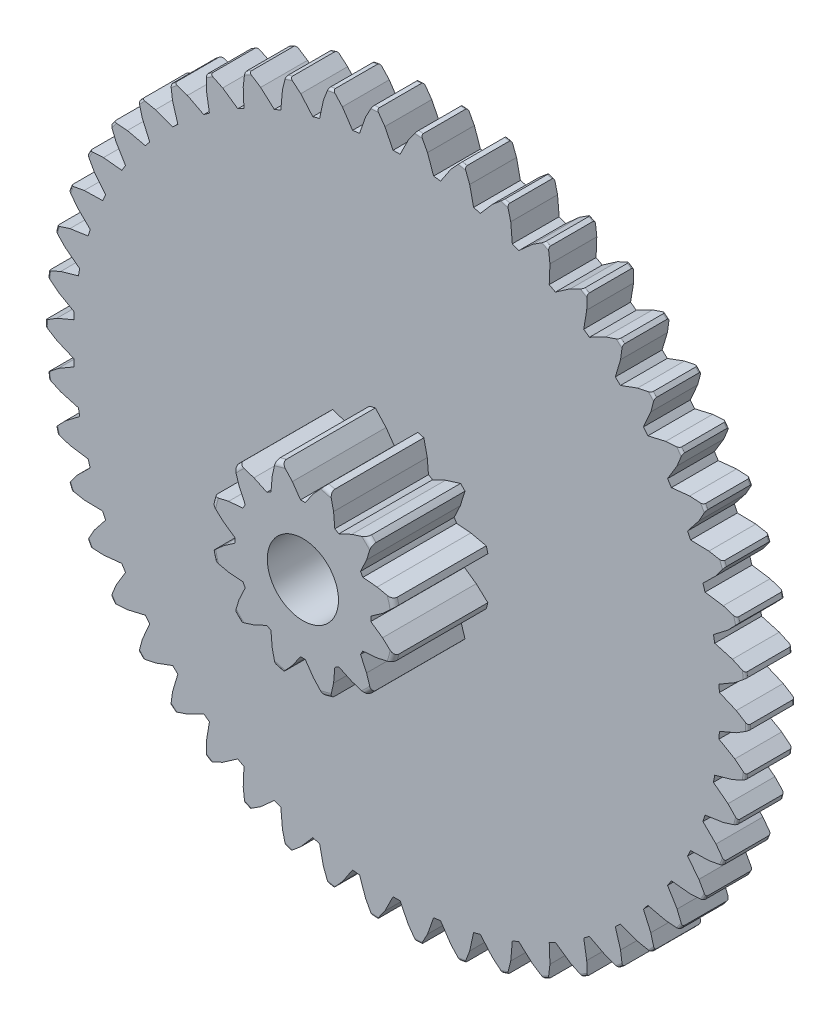
SolidWorks part; units mm, degrees
material "2014-T4"
ref_plane "Alzado" through (0, 0, 0) normal (0, 0, 1) x (1, 0, 0)
ref_plane "Planta" through (0, 0, 0) normal (0, 1, 0) x (1, 0, 0)
ref_plane "Vista lateral" through (0, 0, 0) normal (1, 0, 0) x (0, 0, -1)
sketch "Croquis1" plane through (0, 0, 0) normal (0, 0, 1) x (1, 0, 0)
  circle A0 centre (0, 0) radius 7.5
  dimension "D1" = 15
extrude "Saliente-Extruir1" add sketch "Croquis1" along normal blind 1
sketch "Croquis3" plane through (0, 0, 1) normal (0, 0, 1) x (1, 0, 0)
  circle A0 centre (0, 0) radius 2
  dimension "D1" = 4
extrude "Saliente-Extruir2" add sketch "Croquis3" along normal blind 2
sketch "Croquis4" plane through (0, 0, 3) normal (0, 0, 1) x (1, 0, 0)
  line L0 (0, 0) -> (0, 7.5) construction
  line L1 (-0.5, 7.6) -> (-0.25, 7.25)
  line L2 (-0.25, 7.25) -> (-0.075, 6.8996)
  line L3 (-0.5, 7.6) -> (0.5, 7.6)
  line L4 (0, 7.5) -> (0, 7.8547) construction
  line L5 (0.5, 7.6) -> (0.25, 7.25)
  line L6 (0.25, 7.25) -> (0.075, 6.8996)
  circle A0 centre (0, 0) radius 7.5 construction
  circle A1 centre (0, 0) radius 6.9
  point P11 (0, 6.9)
  point P12 (0, 7.6)
  dimension "D1" = 13.8
  dimension "D2" = 0.5
  dimension "D3" = 0.7
  dimension "D4" = 0.35
  dimension "D5" = 0.25
  dimension "D6" = 0.075
extrude "Cortar-Extruir5" cut sketch "Croquis4" against normal blind 3 contours A1 L6 L5 L3 L1 L2 region at (0, 7.3422, 3)
fillet "Redondeo2" radius 0.05 2 edges at (0, -7.5, 0) (0, -7.5, 1)
pattern_circular "MatrizC3" count 50 over 360 about axis through (0, 0, 1) along (0, 0, -1) of "Cortar-Extruir5"
sketch "Croquis5" plane through (0, 0, 3) normal (0, 0, 1) x (1, 0, 0)
  line L0 (0, 0) -> (0, 3.1284) construction
  line L1 (0.5, 2) -> (-0.5, 2)
  line L2 (-0.05, 1.4491) -> (-0.225, 1.7)
  line L3 (0.225, 1.7) -> (0.5, 2)
  line L4 (-0.225, 1.7) -> (-0.5, 2)
  line L5 (0.05, 1.4491) -> (0.225, 1.7)
  circle A0 centre (0, 0) radius 0.76
  circle A1 centre (0, 0) radius 1.45
  point P16 (0, 2)
  circle M6 centre (0, 0) radius 2
  dimension "D1" = 1.52
  dimension "D2" = 2.9
  dimension "D7" = 2
  dimension "D3" = 0.5
  dimension "D4" = 0.05
  dimension "D5" = 0.225
  dimension "D6" = 1.7
extrude "Cortar-Extruir6" cut sketch "Croquis5" against normal blind 2 contours L0 A1 L5 L3 M6 | A1 L0 L4 L2 M6 region at (-0.15, 1.7925, 3) region at (0.15, 1.7925, 3)
fillet "Redondeo1" radius 0.1 1 edges at (0, -2, 3)
pattern_circular "MatrizC4" count 12 over 360 about axis through (0, 0, 3) along (0, 0, -1) of "Cortar-Extruir6" reverse direction yes
extrude "Cortar-Extruir8" cut sketch "Croquis5<4>" against normal blind 3 contours A0 region at (0, 0, 3)
sketch "Croquis5<4>" plane through (0, 0, 3) normal (0, 0, 1) x (1, 0, 0) same geometry as "Croquis5"
